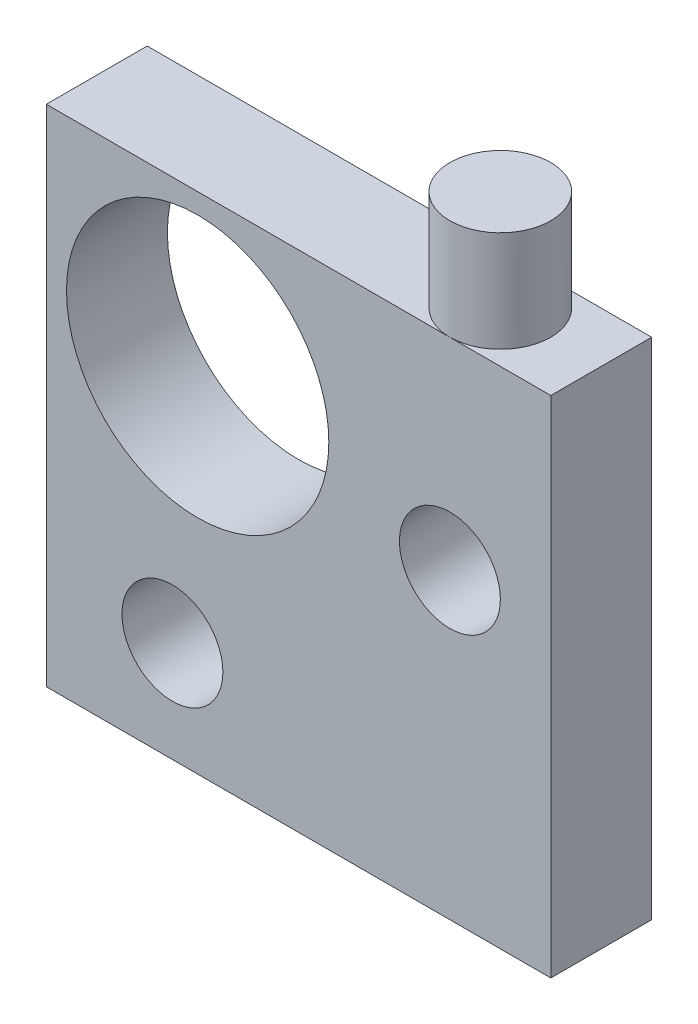
SolidWorks part; units mm, degrees
material "ABS"
ref_plane "前视基准面" through (0, 0, 0) normal (0, 0, 1) x (1, 0, 0)
ref_plane "上视基准面" through (0, 0, 0) normal (0, 1, 0) x (1, 0, 0)
ref_plane "右视基准面" through (0, 0, 0) normal (1, 0, 0) x (0, 0, -1)
sketch "草图1" plane through (0, 0, 0) normal (0, 0, 1) x (1, 0, 0)
  line L1 (-40, 30) -> (40, 30)
  line L2 (-40, 30) -> (-40, -30)
  line L3 (-40, -30) -> (40, -30)
  line L4 (40, 30) -> (40, -30)
  line L5 (-40, 30) -> (40, -30) construction
  line L6 (-40, -30) -> (40, 30) construction
  point P0 (0, 0)
extrude "凸台-拉伸1" add sketch "草图1" along normal blind 10
sketch "草图2" plane through (0, 30, 0) normal (0, 1, 0) x (1, 0, 0)
  circle A0 centre (0, -5) radius 5
  line M2 (40, 0) -> (-40, 0)
  line M3 (-40, 0) -> (-40, -10)
  line M4 (-40, -10) -> (40, -10)
  line M5 (40, -10) -> (40, 0)
extrude "切除-拉伸1" cut sketch "草图2" against normal blind 10 contours A0 M5 M2 M3 M4 | A0 M4 M5 M2 region at (21.9462, 30, 5) region at (-21.9462, 30, 5)
sketch "草图3" plane through (0, 0, 10) normal (0, 0, 1) x (1, 0, 0)
  circle A0 centre (-27.5, -20) radius 5
  circle A1 centre (0, 0) radius 5
  circle A2 centre (-25, 5) radius 13
extrude "切除-拉伸2" cut sketch "草图3" against normal through all contours A1 | A0 | A2
sketch "草图4" plane through (0, 0, 10) normal (0, 0, 1) x (1, 0, 0)
  line L0 (-40, 20) -> (0, 20) construction
  line L1 (40, -30) -> (10, -30)
  line L2 (40, -30) -> (40, 20)
  line L3 (40, 20) -> (10, 20)
  line L4 (10, -30) -> (10, 20)
extrude "切除-拉伸3" cut sketch "草图4" against normal through all
